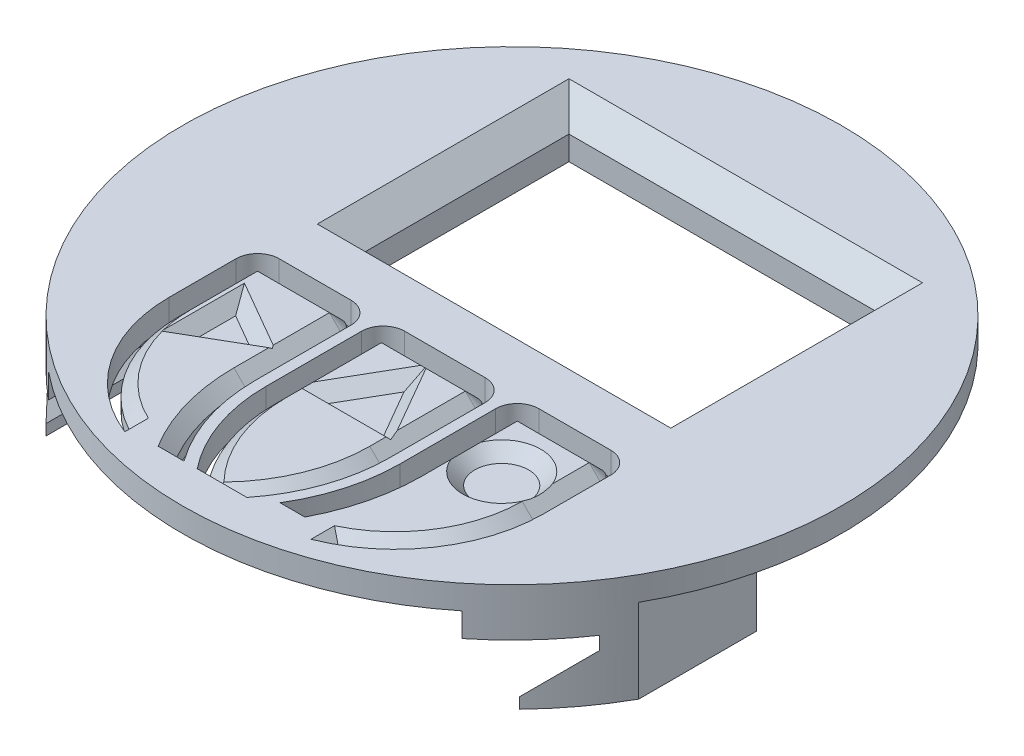
SolidWorks part; units mm, degrees
ref_plane "Front Plane" through (0, 0, 0) normal (0, 0, 1) x (1, 0, 0)
ref_plane "Top Plane" through (0, 0, 0) normal (0, 1, 0) x (1, 0, 0)
ref_plane "Right Plane" through (0, 0, 0) normal (1, 0, 0) x (0, 0, -1)
sketch "Sketch1" plane through (0, 0, 0) normal (0, 1, 0) x (1, 0, 0)
  line L0 (-16.8, 1.5) -> (16.8, 1.5) construction
  line L1 (-16.8, -6.1) -> (16.8, -6.1) construction
  line L2 (-16.8, -6.1) -> (-16.8, 6.1) construction
  line L3 (-16.8, 6.1) -> (16.8, 6.1) construction
  line L4 (16.8, -6.1) -> (16.8, 6.1) construction
  line L5 (-16.8, -6.1) -> (16.8, 6.1) construction
  line L6 (-16.8, 6.1) -> (16.8, -6.1) construction
  line L7 (0, 0) -> (0, -4) construction
  line L8 (-5, -5.4) -> (5, -5.4) construction
  line L9 (-5, -5.4) -> (-5, -2.6) construction
  line L10 (-5, -2.6) -> (5, -2.6) construction
  line L11 (5, -5.4) -> (5, -2.6) construction
  line L12 (-5, -5.4) -> (5, -2.6) construction
  line L13 (-5, -2.6) -> (5, -5.4) construction
  line L14 (0, 0) -> (0, 34.8308) construction
  line L15 (-14.772, -11.5) -> (14.772, -11.5) construction
  line L16 (-12.75, 7.1) -> (12.75, 7.1) construction
  line L17 (-12.75, 7.1) -> (-12.75, 33.2) construction
  line L18 (-12.75, 33.2) -> (12.75, 33.2) construction
  line L19 (12.75, 7.1) -> (12.75, 33.2) construction
  line L20 (-12.75, 7.1) -> (12.75, 33.2) construction
  line L21 (-12.75, 33.2) -> (12.75, 7.1) construction
  line L22 (-12.75, 12.2) -> (12.75, 12.2)
  line L23 (-12.75, 12.2) -> (-12.75, 29.2)
  line L24 (-12.75, 29.2) -> (12.75, 29.2)
  line L25 (12.75, 12.2) -> (12.75, 29.2)
  line L26 (-12.75, 12.2) -> (12.75, 29.2) construction
  line L27 (-12.75, 29.2) -> (12.75, 12.2) construction
  line L29 (-4.5, -3.6738) -> (-4.5, 4.3)
  line L30 (-3.5, 5.3) -> (3.5, 5.3)
  line L31 (4.5, -3.6738) -> (4.5, 4.3)
  line L32 (-15.6377, 4.3) -> (-15.6377, -1.291)
  line L33 (-13.8377, 6.1) -> (-7.8377, 6.1)
  line L35 (6.8377, -3.6738) -> (6.8377, 4.3)
  line L36 (7.8377, 5.3) -> (13.8377, 5.3)
  line L37 (14.8377, -1.291) -> (14.8377, 4.3)
  line L38 (6.8377, -3.6738) -> (14.8377, 5.3) construction
  line L39 (6.8377, 5.3) -> (14.8377, -1.291) construction
  line L41 (-14.8377, -1.291) -> (-14.8377, 4.3)
  line L42 (-13.8377, 5.3) -> (-7.8377, 5.3)
  line L43 (-6.8377, -3.6738) -> (-6.8377, 4.3)
  line L44 (-14.8377, -1.291) -> (-6.8377, 5.3) construction
  line L45 (-14.8377, 5.3) -> (-6.8377, -3.6738) construction
  line L46 (-2.8, -11.5) -> (-2, -11.5)
  line L47 (-5.1594, -3.6738) -> (-5.1594, 4.3)
  line L48 (-3.3594, 6.1) -> (3.3594, 6.1)
  line L49 (5.1594, -3.6738) -> (5.1594, 4.3)
  line L50 (2.8, -11.5) -> (2, -11.5)
  line L51 (-6.0377, 4.3) -> (-6.0377, -3.6738)
  line L52 (15.6377, -1.291) -> (15.6377, 4.3)
  line L53 (13.8377, 6.1) -> (7.8377, 6.1)
  line L54 (6.0377, 4.3) -> (6.0377, -3.6738)
  line L55 (-8.7689, -11.5) -> (-8.7689, -12.4022)
  line L56 (-4.7689, -11.5) -> (-3.8406, -11.5)
  line L57 (3.8406, -11.5) -> (4.7689, -11.5)
  line L58 (8.7689, -11.5) -> (8.7689, -12.4022)
  line L59 (-4.5, -3.6738) -> (4.5, -3.6738) construction
  circle A0 centre (11.45, 1.5) radius 2.5 construction
  circle A1 centre (0, 1.5) radius 2.5 construction
  circle A2 centre (-11.45, 1.5) radius 2.5 construction
  circle A3 centre (0, 11.6956) radius 25 construction
  circle A4 centre (0, 11.6956) radius 27.5
  arc A5 (-14.8377, -1.291) -> (-8.7689, -11.5) centre (-3.2164, -1.291) ccw
  arc A6 (-6.8377, -3.6738) -> (-4.7689, -11.5) centre (9, -3.6738) ccw
  arc A7 (4.5, -3.6738) -> (2, -11.5) centre (-9, -3.6738) cw
  arc A8 (-4.5, -3.6738) -> (-2, -11.5) centre (9, -3.6738) ccw
  arc A9 (6.8377, -3.6738) -> (4.7689, -11.5) centre (-9, -3.6738) cw
  arc A10 (14.8377, -1.291) -> (8.7689, -11.5) centre (3.2164, -1.291) cw
  arc A11 (4.5, 4.3) -> (3.5, 5.3) centre (3.5, 4.3) ccw
  arc A12 (-3.5, 5.3) -> (-4.5, 4.3) centre (-3.5, 4.3) ccw
  arc A13 (-2.8, -11.5) -> (-5.1594, -3.6738) centre (9, -3.6738) cw
  arc A14 (-3.3594, 6.1) -> (-5.1594, 4.3) centre (-3.3594, 4.3) ccw
  arc A15 (3.3594, 6.1) -> (5.1594, 4.3) centre (3.3594, 4.3) cw
  arc A16 (2.8, -11.5) -> (5.1594, -3.6738) centre (-9, -3.6738) ccw
  arc A17 (-15.6377, -1.291) -> (-8.7689, -12.4022) centre (-3.2164, -1.291) ccw
  arc A18 (-6.0377, -3.6738) -> (-3.8406, -11.5) centre (9, -3.6738) ccw
  arc A19 (6.0377, -3.6738) -> (3.8406, -11.5) centre (-9, -3.6738) cw
  arc A20 (15.6377, -1.291) -> (8.7689, -12.4022) centre (3.2164, -1.291) cw
  arc A21 (-6.8377, 4.3) -> (-7.8377, 5.3) centre (-7.8377, 4.3) ccw
  arc A22 (-13.8377, 5.3) -> (-14.8377, 4.3) centre (-13.8377, 4.3) ccw
  arc A23 (15.6377, 4.3) -> (13.8377, 6.1) centre (13.8377, 4.3) ccw
  arc A24 (7.8377, 6.1) -> (6.0377, 4.3) centre (7.8377, 4.3) ccw
  arc A25 (-6.0377, 4.3) -> (-7.8377, 6.1) centre (-7.8377, 4.3) ccw
  arc A26 (-13.8377, 6.1) -> (-15.6377, 4.3) centre (-13.8377, 4.3) ccw
  arc A27 (14.8377, 4.3) -> (13.8377, 5.3) centre (13.8377, 4.3) ccw
  arc A28 (7.8377, 5.3) -> (6.8377, 4.3) centre (7.8377, 4.3) ccw
  point P0 (0, 0)
  point P16 (0, -4)
  point P21 (0, 20.15)
  point P29 (0, 20.7)
  point P66 (0, 6.1)
  dimension "D6" = 28.25
  dimension "D7" = 5
  dimension "D11" = 50
  dimension "D18" = 55
  dimension "D19" = 18
  dimension "D20" = 4
  dimension "D21" = 1
  dimension "D24" = 1.8
  dimension "D36" = 1
  dimension "D40" = 1.8
  dimension "D41" = 1
  dimension "D1" = 12.2
  dimension "D2" = 33.6
  dimension "D3" = 4.6
  dimension "D4" = 5.35
  dimension "D5" = 16.8
  dimension "D8" = 10
  dimension "D9" = 3.5
  dimension "D10" = 0.7
  dimension "D12" = 26.1
  dimension "D13" = 25.5
  dimension "D14" = 1
  dimension "D15" = 4
  dimension "D16" = 17
  dimension "D17" = 13
  dimension "D22" = 0.8
  dimension "D23" = 0.8
  dimension "D25" = 9
  dimension "D26" = 8
  dimension "D29" = 8
  dimension "D31" = 4
  dimension "D32" = 4
  dimension "D33" = 0.8
  dimension "D34" = 0.8
  dimension "D35" = 0.8
  dimension "D37" = 0.8
  dimension "D38" = 0.8
  dimension "D39" = 0.8
extrude "Boss-Extrude1" add sketch "Sketch1" along normal blind 2
chamfer "Chamfer1" distance 2 angle 45 4 edges at (12.75, 2, -20.7) (0, 2, -12.2) (-12.75, 2, -20.7) (0, 2, -29.2)
sketch "Sketch3" plane through (0, 0, 0) normal (0, -1, 0) x (1, 0, 0)
  line L6 (0, 0) -> (0, -34.8308) construction
  line L7 (-13.75, -30.2) -> (13.75, -30.2)
  line L8 (-13.75, -30.2) -> (-13.75, -11.2)
  line L9 (-13.75, -11.2) -> (13.75, -11.2)
  line L10 (13.75, -30.2) -> (13.75, -11.2)
  line L11 (-13.75, -30.2) -> (13.75, -11.2) construction
  line L12 (-13.75, -11.2) -> (13.75, -30.2) construction
  line L13 (-12.75, -12.2) -> (12.75, -12.2) construction
  line L14 (-15.25, -31.7) -> (15.25, -31.7)
  line L15 (-15.25, -31.7) -> (-15.25, -10.2)
  line L17 (15.25, -31.7) -> (15.25, -10.2)
  line L18 (-15.25, -31.7) -> (15.25, -9.7) construction
  line L19 (-15.25, -9.7) -> (15.25, -31.7) construction
  line L20 (-12.75, -29.2) -> (12.75, -29.2) construction
  line L21 (-12.75, -12.2) -> (-12.75, -29.2) construction
  line L26 (15.25, -10.2) -> (-15.25, -10.2)
  line L28 (0, 0) -> (0, 18.5347) construction
  point P6 (0, -20.7)
  point P21 (0, -20.7)
  point P43 (19.8795, -8.9292)
  dimension "D2" = 1
  dimension "D5" = 1
  dimension "D7" = 1
  dimension "D8" = 1.5
  dimension "D9" = 1.5
  dimension "D10" = 1
  dimension "D14" = 1.5
  dimension "D15" = 1.5
extrude "Boss-Extrude2" add sketch "Sketch3" along normal blind 3
sketch "Sketch6" plane through (0, 2, 0) normal (0, 1, 0) x (1, 0, 0)
  line L0 (-10.8377, 5.3) -> (-10.8377, -4.8362) construction
  line L1 (0, 5.3) -> (0, -5.3387) construction
  line L2 (10.8377, 5.3) -> (10.8377, -7.1794) construction
  line L3 (-14.8377, -1.291) -> (-14.8377, 4.3) construction
  line L4 (-6.8377, 4.3) -> (-6.8377, -3.6738) construction
  line L5 (-13.8377, 5.3) -> (-7.8377, 5.3) construction
  line L6 (-3.5, 5.3) -> (3.5, 5.3) construction
  line L7 (7.8377, 5.3) -> (13.8377, 5.3) construction
  line L8 (6.8377, -3.6738) -> (6.8377, 4.3) construction
  line L9 (14.8377, 4.3) -> (14.8377, -1.291) construction
  line L10 (-12.5214, 1.1547) -> (-9.5214, -0.5774)
  line L11 (-9.5214, -0.5774) -> (-12.5214, -2.3094)
  line L12 (-12.5214, -2.3094) -> (-12.5214, 1.1547)
  line L13 (0, 2.6815) -> (-2.3094, -1.3185)
  line L14 (-2.3094, -1.3185) -> (2.3094, -1.3185)
  line L15 (2.3094, -1.3185) -> (0, 2.6815)
  line L16 (-9.5214, -0.5774) -> (-13.5141, -0.8195) construction
  circle A0 centre (10.8377, 0) radius 2.25
  point P29 (0, 0)
  dimension "D5" = 4.5
  dimension "D1" = 60
  dimension "D2" = 4
  dimension "D3" = 3
  dimension "D4" = 60
extrude "Cut-Extrude2" cut sketch "Sketch6" against normal blind 1
sketch "Sketch7" plane through (0, 0, 0) normal (0, -1, 0) x (1, 0, 0)
  line L0 (12.95, -1.5) -> (9.95, -1.5)
  line L1 (-16.8, -1.5) -> (16.8, -1.5) construction
  line L2 (1.5, -1.5) -> (-1.5, -1.5)
  line L3 (-9.95, -1.5) -> (-12.95, -1.5)
  arc A0 (12.95, -1.5) -> (9.95, -1.5) centre (11.45, -1.5) cw
  arc A1 (1.5, -1.5) -> (-1.5, -1.5) centre (0, -1.5) cw
  arc A2 (-9.95, -1.5) -> (-12.95, -1.5) centre (-11.45, -1.5) cw
  point P4 (0, 0)
  point P6 (0, 0)
  point P11 (0, -1.5)
  point P16 (-11.45, -1.5)
  dimension "D1" = 1.5
revolve "Revolve1" add sketch "Sketch7" angle 180 about L0 reverse direction yes
chamfer "Chamfer2" distance 1 angle 45 7 edges at (-11.0214, 2, 1.4434) (-11.0214, 2, -0.2887) (-12.5214, 2, 0.5774) (0, 2, 1.3185) (-1.1547, 2, -0.6815) (1.1547, 2, -0.6815) (10.8377, 2, 2.25)
chamfer "Chamfer3" distance 1 angle 45 26 edges at (-7.1305, 2, -5.0071) (-10.8377, 2, -5.3) (-14.5448, 2, -5.0071) (-14.8377, 2, -1.5045) (-13.2059, 2, 7.2293) (-8.7689, 2, 11.9511) (-6.8377, 2, -0.3131) (-6.3117, 2, 7.7213) (-4.3047, 2, 11.5) (-2.4, 2, 11.5) (-3.8598, 2, 7.7817) (-4.5, 2, -0.3131) (-4.2071, 2, -5.0071) (0, 2, -5.3) (4.2071, 2, -5.0071) (4.5, 2, -0.3131) (2.4, 2, 11.5) (3.8598, 2, 7.7817) (8.7689, 2, 11.9511) (13.2059, 2, 7.2293) (14.8377, 2, -1.5045) (14.5448, 2, -5.0071) (10.8377, 2, -5.3) (7.1305, 2, -5.0071) (6.8377, 2, -0.3131) (6.3117, 2, 7.7213)
sketch "Sketch8" plane through (0, 0, 0) normal (0, -1, 0) x (1, 0, 0)
  line L0 (-17.25, 9.7214) -> (-17.25, -7.1)
  line L1 (-17.25, -7.1) -> (17.25, -7.1)
  line L2 (17.25, -7.1) -> (17.25, 9.7214)
  line L3 (-24, 1.7301) -> (-24, -8.1)
  line L4 (-24, -8.1) -> (24, -8.1)
  line L5 (24, -8.1) -> (24, 1.7301)
  line L7 (0, 0) -> (0, 21.2701) construction
  line L8 (-7.8377, -6.1) -> (-13.8377, -6.1) construction
  circle A0 centre (0, -11.6956) radius 27.5 construction
  arc A1 (-17.25, 9.7214) -> (-24, 1.7301) centre (0, -11.6956) ccw
  arc A2 (17.25, 9.7214) -> (24, 1.7301) centre (0, -11.6956) cw
  dimension "D1" = 1
  dimension "D2" = 48
  dimension "D3" = 34.5
  dimension "D4" = 1
extrude "Boss-Extrude3" add sketch "Sketch8" along normal blind 7
sketch "Sketch9" plane through (0, 0, -7.1) normal (0, 0, 1) x (1, 0, 0)
  line L0 (22.75, -2) -> (-22.75, -2)
  line L1 (-22.75, -2) -> (-22.75, -3.1)
  line L2 (-22.75, -3.1) -> (-19.75, -6.1)
  line L3 (-19.75, -6.1) -> (-19.75, -9.1171)
  line L4 (-19.75, -9.1171) -> (19.75, -9.1171)
  line L5 (19.75, -9.1171) -> (19.75, -6.1)
  line L6 (19.75, -6.1) -> (22.75, -3.1)
  line L7 (22.75, -3.1) -> (22.75, -2)
  line L8 (0, 0) -> (0, -24.2484) construction
  line L9 (0, 0) -> (-29.9869, 0) construction
  point P2 (19.5891, -4.5374)
  point P12 (16.6626, -7.1)
  dimension "D1" = 2
  dimension "D2" = 1.1
  dimension "D3" = 135
  dimension "D4" = 3
  dimension "D5" = 45.5
extrude "Cut-Extrude3" cut sketch "Sketch9" along normal through all
